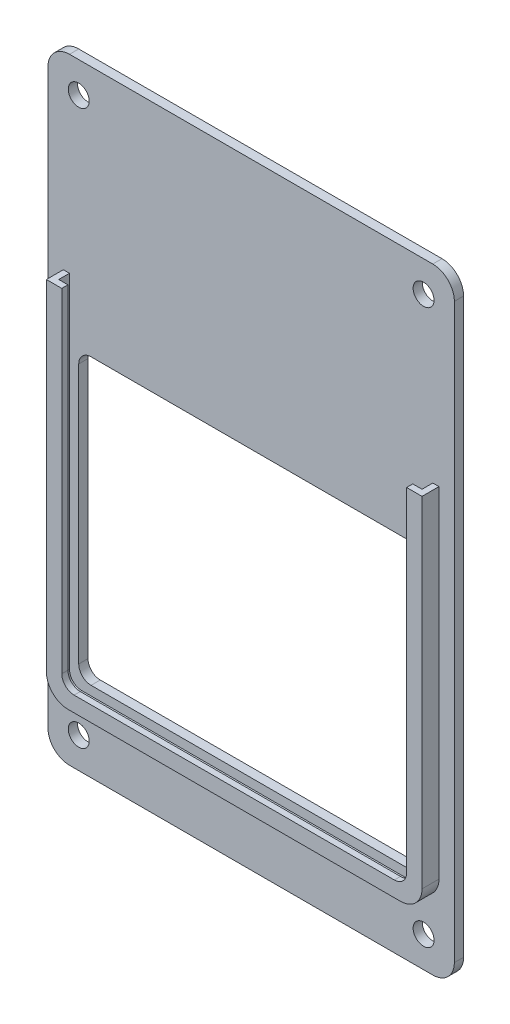
SolidWorks part; units mm, degrees
material "ABS"
ref_plane "Спереди" through (0, 0, 0) normal (0, 0, 1) x (1, 0, 0)
ref_plane "Сверху" through (0, 0, 0) normal (0, 1, 0) x (1, 0, 0)
ref_plane "Справа" through (0, 0, 0) normal (1, 0, 0) x (0, 0, -1)
sketch "Эскиз1" plane through (0, 0, 0) normal (0, 0, 1) x (1, 0, 0)
  line L1 (-33, -50) -> (33, -50)
  line L2 (-33, -50) -> (-33, 50)
  line L3 (-33, 50) -> (33, 50)
  line L4 (33, -50) -> (33, 50)
  line L5 (-33, -50) -> (33, 50) construction
  line L6 (-33, 50) -> (33, -50) construction
  point P0 (0, 0)
  dimension "D1" = 100
  dimension "D2" = 66
extrude "Бобышка-Вытянуть1" add sketch "Эскиз1" along normal blind 1.5 contours L2 L3 L4 L1
fillet "Скругление1" radius 3.5 4 edges at (-33, -50, 0.75) (33, -50, 0.75) (33, 50, 0.75) (-33, 50, 0.75)
sketch "Эскиз2" plane through (0, 0, 1.5) normal (0, 0, 1) x (1, 0, 0)
  line L0 (-29.5, -50) -> (29.5, -50) construction
  line L1 (-33, -50) -> (-24, -50)
  line L2 (-33, -50) -> (-33, -41)
  line L3 (-33, -41) -> (-24, -41)
  line L4 (-24, -50) -> (-24, -41)
  line L5 (33, -50) -> (24, -50)
  line L6 (33, -50) -> (33, -41)
  line L7 (33, -41) -> (24, -41)
  line L8 (24, -50) -> (24, -41)
  line L9 (-28, 9.2) -> (28, 9.2)
  line L10 (-28, 9.2) -> (-28, -37)
  line L11 (-28, -37) -> (28, -37)
  line L12 (28, 9.2) -> (28, -37)
  line L13 (-33, -46.5) -> (-33, 46.5) construction
  line L14 (33, -46.5) -> (33, 46.5) construction
  dimension "D1" = 46.2
  dimension "D2" = 5
  dimension "D3" = 5
  dimension "D4" = 13
  dimension "D5" = 9
extrude "Вырез-Вытянуть1" cut sketch "Эскиз2" against normal blind 1.5 contours L12 L9 L10 L3 L4 L11 L8 L7 region at (0, -13.9, 1.5)
fillet "Скругление2" radius 2 4 edges at (-28, -37, 0.75) (28, -37, 0.75) (-28, 9.2, 0.75) (28, 9.2, 0.75)
sketch "Эскиз3" plane through (0, 0, 1.5) normal (0, 0, 1) x (1, 0, 0)
  line L0 (-26, 9.2) -> (26, 9.2) construction
  line L1 (-28, -37) -> (28, -37)
  line L2 (-28, -37) -> (-28, 9.2)
  line L3 (-28, 9.2) -> (28, 9.2)
  line L4 (28, -37) -> (28, 9.2)
  line L5 (-29.5, -38.5) -> (29.5, -38.5)
  line L6 (-29.5, -38.5) -> (-29.5, 19.2)
  line L7 (-29.5, 19.2) -> (29.5, 19.2)
  line L8 (29.5, -38.5) -> (29.5, 19.2)
  line L10 (-26, -37) -> (26, -37) construction
  line L11 (28, 7.2) -> (28, -35) construction
  line L12 (-28, 7.2) -> (-28, -35) construction
  line L14 (-30.5, 19.2) -> (30.5, 19.2)
  line L15 (-30.5, 19.2) -> (-30.5, -39.5)
  line L16 (-30.5, -39.5) -> (30.5, -39.5)
  line L17 (30.5, 19.2) -> (30.5, -39.5)
  dimension "D1" = 1.5
  dimension "D2" = 1.5
  dimension "D3" = 1.5
  dimension "D4" = 10
  dimension "D5" = 1
  dimension "D6" = 1
  dimension "D7" = 1
extrude "Бобышка-Вытянуть2" add sketch "Эскиз3" along normal blind 1.75 contours L17 L14 L8 L5 L6 L15 L16 region at (0, -39.3466, 1.5)
fillet "Скругление3" radius 2 2 edges at (29.5, -38.5, 2.375) (-29.5, -38.5, 2.375)
sketch "Эскиз4" plane through (0, 0, 3.25) normal (0, 0, 1) x (1, 0, 0)
  line L0 (-28, 7.2) -> (-28, -35) construction
  line L1 (-30.5, -39.5) -> (30.5, -39.5)
  line L2 (-30.5, -39.5) -> (-30.5, 19.2)
  line L3 (-30.5, 19.2) -> (30.5, 19.2)
  line L4 (30.5, -39.5) -> (30.5, 19.2)
  line L5 (-28, 19.2) -> (28, 19.2)
  line L6 (-28, 19.2) -> (-28, -37)
  line L7 (-28, -37) -> (28, -37)
  line L8 (28, 19.2) -> (28, -37)
  line L9 (-26, -37) -> (26, -37) construction
  line L10 (28, 7.2) -> (28, -35) construction
  line M4 (30.5, -39.5) -> (30.5, 19.2)
  line M5 (30.5, 19.2) -> (29.5, 19.2)
  line M6 (29.5, 19.2) -> (29.5, -36.5)
  arc M7 (29.5, -36.5) -> (27.5, -38.5) centre (27.5, -36.5) cw
  line M8 (27.5, -38.5) -> (-27.5, -38.5)
  arc M9 (-27.5, -38.5) -> (-29.5, -36.5) centre (-27.5, -36.5) cw
  line M10 (-29.5, -36.5) -> (-29.5, 19.2)
  line M11 (-29.5, 19.2) -> (-30.5, 19.2)
  line M12 (-30.5, 19.2) -> (-30.5, -39.5)
  line M13 (-30.5, -39.5) -> (30.5, -39.5)
extrude "Бобышка-Вытянуть3" add sketch "Эскиз4" along normal blind 1 contours M13 M4 M5 M6 M7 M8 M9 M10 M11 M12 | L3 L8 L7 L6 M10 M9 M8 M7 M6 region at (-29.6534, -10.15, 3.25) region at (-28.75, 18.3748, 3.25)
fillet "Скругление4" radius 2 2 edges at (-28, -37, 3.75) (28, -37, 3.75)
fillet "Скругление5" radius 3.5 2 edges at (-30.5, -39.5, 2.875) (30.5, -39.5, 2.875)
sketch "Эскиз5" plane through (0, 0, 0) normal (0, 0, -1) x (-1, 0, 0)
  line L1 (-24, -38.5) -> (24, -38.5)
  line L2 (-24, -38.5) -> (-24, -48.5)
  line L3 (-24, -48.5) -> (24, -48.5)
  line L4 (24, -38.5) -> (24, -48.5)
  line L5 (-31.5, 48.5) -> (31.5, 48.5)
  line L6 (-31.5, 48.5) -> (-31.5, 10.7)
  line L7 (-31.5, 10.7) -> (31.5, 10.7)
  line L8 (31.5, 48.5) -> (31.5, 10.7)
  line L9 (31.5, 48.5) -> (24, 48.5)
  line L10 (31.5, 48.5) -> (31.5, 41)
  line L11 (31.5, 41) -> (24, 41)
  line L12 (24, 48.5) -> (24, 41)
  line L13 (-31.5, 48.5) -> (-24, 48.5)
  line L14 (-31.5, 48.5) -> (-31.5, 41)
  line L15 (-31.5, 41) -> (-24, 41)
  line L16 (-24, 48.5) -> (-24, 41)
  line L18 (-33, -46.5) -> (-33, 46.5) construction
  line L19 (29.5, 50) -> (-29.5, 50) construction
  line L20 (29.5, -50) -> (-29.5, -50) construction
  dimension "D1" = 7.5
  dimension "D2" = 37.8
  dimension "D3" = 63
  dimension "D4" = 1.5
  dimension "D5" = 1.5
  dimension "D6" = 10
  dimension "D7" = 48
  dimension "D8" = 1.5
  dimension "D9" = 9
extrude "Бобышка-Вытянуть4" add sketch "Эскиз5" along normal blind 1 contours L5 L16 L15 L6 L7 L8 L11 L12 | L4 L1 L2 L3 region at (0, -43.5, 0) region at (0, 28.8488, 0)
fillet "Скругление6" radius 1.5 10 edges at (24, 48.5, -0.5) (31.5, 41, -0.5) (31.5, 10.7, -0.5) (-31.5, 10.7, -0.5) (-31.5, 41, -0.5) (-24, 48.5, -0.5) (-24, -48.5, -0.5) (-24, -38.5, -0.5) (24, -38.5, -0.5) (24, -48.5, -0.5)
fillet "Скругление7" radius 4 2 edges at (-24, 41, -0.5) (24, 41, -0.5)
sketch "Эскиз6" plane through (0, 0, 1.5) normal (0, 0, 1) x (1, 0, 0)
  line L1 (-29.5, 50) -> (29.5, 50) construction
  line L2 (-33, -46.5) -> (-33, 46.5) construction
  line L3 (33, -46.5) -> (33, 46.5) construction
  line L4 (-29.5, -50) -> (29.5, -50) construction
  point P0 (-28, 45)
  point P1 (28, 45)
  point P3 (-28, -45)
  point P4 (28, -45)
  dimension "D1" = 5
  dimension "D2" = 5
  dimension "D3" = 5
  dimension "D4" = 5
hole_wizard "Отверстие с зазором M31" positions "Эскиз7" profile "Эскиз8" hole size "M3" standard "DIN" end condition through all
sketch "Эскиз7" plane through (0, 0, 1.5) normal (0, 0, 1) x (1, 0, 0)
  point P0 (-28, 45)
  point P3 (28, 45)
  point P6 (28, -45)
  point P9 (-28, -45)
sketch "Эскиз8" plane through (-28, 45, 1.5) normal (1, 0, 0) x (0, -1, 0)
  line L0 (0, 0) -> (0, 2.5)
  line L1 (0, 2.5) -> (1.7, 2.5)
  line L2 (1.7, 2.5) -> (1.7, 0)
  line L5 (1.7, 0) -> (0, 0)
  line L11 (0, -6.35) -> (0, 107.95) construction
  dimension "Диаметр сквозного отверстия" = 3.4
  dimension "Глубина сквозного отверстия" = 2.5
sketch "Эскиз9" plane through (0, 0, -1) normal (0, 0, -1) x (-1, 0, 0)
  line L0 (-23, 45) -> (-23, 47)
  line L1 (-22.5, 47.5) -> (22.5, 47.5)
  line L2 (23, 47) -> (23, 45)
  line L3 (28, 40) -> (30, 40)
  line L4 (30.5, 39.5) -> (30.5, 12.2)
  line L5 (30, 11.7) -> (-30, 11.7)
  line L6 (-30.5, 12.2) -> (-30.5, 39.5)
  line L7 (-30, 40) -> (-28, 40)
  line L8 (-22.5, -39.5) -> (22.5, -39.5)
  line L9 (23, -40) -> (23, -47)
  line L10 (22.5, -47.5) -> (-22.5, -47.5)
  line L11 (-23, -47) -> (-23, -40)
  line L12 (-22.5, 48.5) -> (22.5, 48.5) construction
  line L14 (-31.5, 39.5) -> (-31.5, 12.2) construction
  line L15 (-24, -40) -> (-24, -47) construction
  line L16 (24, -40) -> (24, -47) construction
  line L17 (-22.5, -38.5) -> (22.5, -38.5) construction
  line L18 (-22.5, -48.5) -> (22.5, -48.5) construction
  line L19 (31.5, 39.5) -> (31.5, 12.2) construction
  line L20 (30, 41) -> (28, 41) construction
  line L21 (24, 47) -> (24, 45) construction
  line L22 (-30, 41) -> (-28, 41) construction
  line L23 (-24, 47) -> (-24, 45) construction
  line L24 (-30, 10.7) -> (30, 10.7) construction
  arc A0 (22.5, -39.5) -> (23, -40) centre (22.5, -40) cw
  arc A1 (23, -47) -> (22.5, -47.5) centre (22.5, -47) cw
  arc A2 (-22.5, -47.5) -> (-23, -47) centre (-22.5, -47) cw
  arc A3 (-22.5, -39.5) -> (-23, -40) centre (-22.5, -40) ccw
  arc A4 (-30.5, 39.5) -> (-30, 40) centre (-30, 39.5) cw
  arc A5 (-30, 11.7) -> (-30.5, 12.2) centre (-30, 12.2) cw
  arc A6 (30.5, 12.2) -> (30, 11.7) centre (30, 12.2) cw
  arc A7 (30, 40) -> (30.5, 39.5) centre (30, 39.5) cw
  arc A8 (22.5, 47.5) -> (23, 47) centre (22.5, 47) cw
  arc A9 (-23, 47) -> (-22.5, 47.5) centre (-22.5, 47) cw
  arc A10 (23, 45) -> (28, 40) centre (28, 45) ccw
  arc A11 (-23, 45) -> (-28, 40) centre (-28, 45) cw
  dimension "D13" = 0.5
  dimension "D14" = 5
  dimension "D1" = 1
  dimension "D2" = 1
  dimension "D3" = 1
  dimension "D4" = 1
  dimension "D5" = 1
  dimension "D6" = 1
  dimension "D7" = 1
  dimension "D8" = 1
  dimension "D9" = 1
  dimension "D10" = 1
  dimension "D11" = 1
  dimension "D12" = 1
extrude "Вырез-Вытянуть3" cut sketch "Эскиз9" against normal up to surface (1 mm away) up to face at (-26.3, 45, 0)
